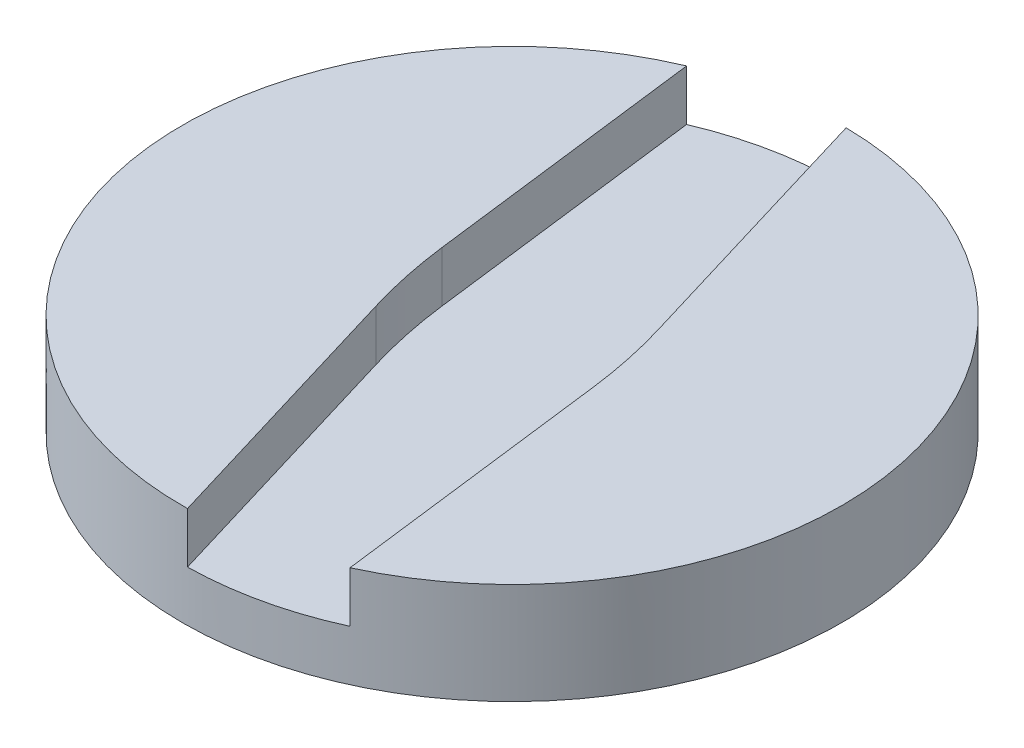
SolidWorks part; units mm, degrees
ref_plane "Alzado" through (0, 0, 0) normal (0, 0, 1) x (1, 0, 0)
ref_plane "Planta" through (0, 0, 0) normal (0, 1, 0) x (1, 0, 0)
ref_plane "Vista lateral" through (0, 0, 0) normal (1, 0, 0) x (0, 0, -1)
sketch "Croquis1" plane through (0, 0, 0) normal (0, 1, 0) x (1, 0, 0)
  circle A0 centre (0, 0) radius 13
  dimension "D1" = 26
extrude "Saliente-Extruir1" add sketch "Croquis1" along normal blind 4
sketch "Croquis3" plane through (0, 4, 0) normal (0, 1, 0) x (1, 0, 0)
  circle A0 centre (0, 0) radius 3.5 construction
  dimension "D1" = 7
sketch "Croquis6" plane through (0, 4, 0) normal (0, 1, 0) x (1, 0, 0)
  line L0 (0, 0) -> (0, 13) construction
  line L1 (0, 0.115) -> (0, -3.7) construction
  line L2 (-16.2152, 1.9838) -> (-1.9003, 3.0576)
  line L3 (-1.9003, 3.0576) -> (-1.9003, -3.0576) construction
  line L4 (-13.9629, -2.1527) -> (-1.9003, -3.0576)
  line L5 (-16.2152, 1.9838) -> (-15.4003, 2.045)
  line L6 (-13.9629, -2.1527) -> (-16.8535, -1.9359)
  line L7 (13.9629, -2.1527) -> (1.9003, -3.0576)
  line L8 (16.2152, 1.9838) -> (1.9003, 3.0576)
  line L9 (-16.2152, 1.9838) -> (-16.8535, -1.9359)
  line L10 (16.2152, 1.9838) -> (13.9629, -2.1527)
  arc A0 (-1.9003, -3.0576) -> (1.9003, -3.0576) centre (0, 0) ccw
  circle A1 centre (0, 0) radius 13 construction
  arc A2 (1.9003, 3.0576) -> (-1.9003, 3.0576) centre (0, 0) ccw
  point P10 (0, 3.6)
  point P14 (-7, 0)
  dimension "D4" = 3.6
  dimension "D1" = 85.71
  dimension "D2" = 85.71
  dimension "D3" = 4.71
sketch "Croquis4" plane through (0, 4, 0) normal (0, 1, 0) x (1, 0, 0)
  line L4 (-3.0086, -2.3501) -> (0.8321, -15.1143)
  line L5 (5.7068, -14.0838) -> (4.0531, -0.8573)
  line L6 (3.3595, 2.4242) -> (-0.4812, 15.1885)
  line L7 (-5.3559, 14.158) -> (-3.7023, 0.9314)
  circle A0 centre (0, 0) radius 3.5 construction
  arc A6 (0.8321, -15.1143) -> (5.7068, -14.0838) centre (3.2261, -14.394) ccw
  arc A7 (-0.4812, 15.1885) -> (-5.3559, 14.158) centre (-2.8752, 14.4682) ccw
  arc A8 (-3.4243, -0.7239) -> (-3.0086, -2.3501) centre (16.1432, 3.4126) ccw
  arc A9 (-3.7023, 0.9314) -> (-3.4243, -0.7239) centre (16.1432, 3.4126) ccw
  arc A10 (3.7752, 0.7981) -> (3.3595, 2.4242) centre (-15.7924, -3.3384) ccw
  arc A11 (4.0531, -0.8573) -> (3.7752, 0.7981) centre (-15.7924, -3.3384) ccw
extrude "Cortar-Extruir1" cut sketch "Croquis4" against normal blind 2
